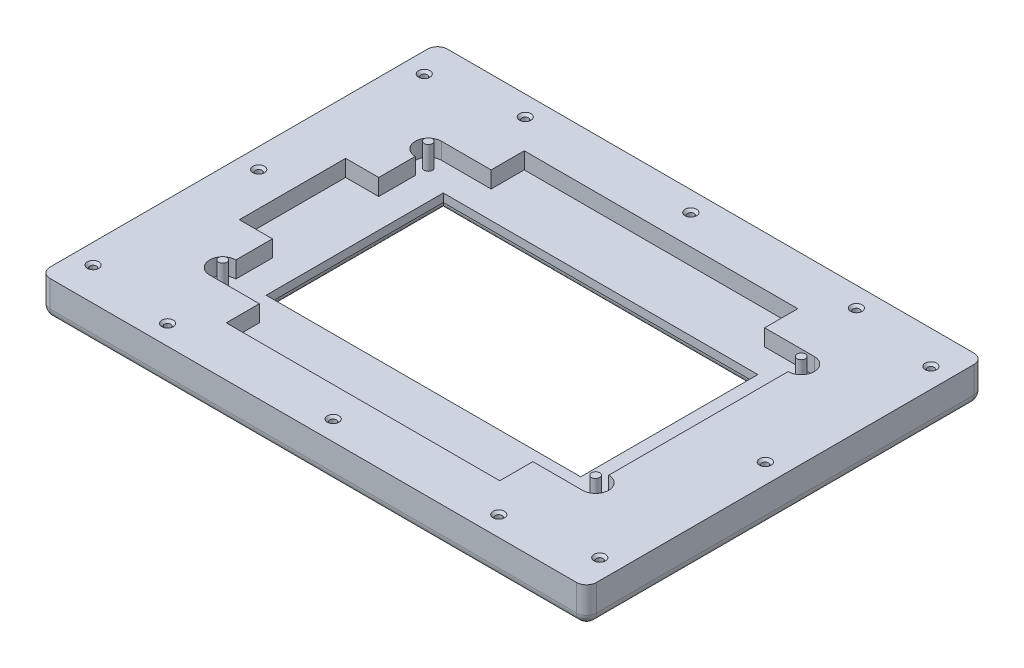
SolidWorks part; units mm, degrees
ref_plane "Front Plane" through (0, 0, 0) normal (0, 0, 1) x (1, 0, 0)
ref_plane "Top Plane" through (0, 0, 0) normal (0, 1, 0) x (1, 0, 0)
ref_plane "Right Plane" through (0, 0, 0) normal (1, 0, 0) x (0, 0, -1)
sketch "Sketch1" plane through (0, 0, 0) normal (0, 1, 0) x (1, 0, 0)
  line L1 (0, 0) -> (165, 0)
  line L2 (0, 0) -> (0, 120)
  line L3 (0, 120) -> (165, 120)
  line L4 (165, 0) -> (165, 120)
  dimension "D1" = 165
  dimension "D2" = 120
extrude "Boss-Extrude1" add sketch "Sketch1" along normal blind 6
sketch "Sketch3" plane through (0, 6, 0) normal (0, 1, 0) x (1, 0, 0)
  line L4 (5, 115) -> (5, 5)
  line L5 (5, 5) -> (160, 5)
  line L6 (160, 5) -> (160, 115)
  line L7 (160, 115) -> (5, 115)
  line L8 (0, 120) -> (0, 0)
  line L9 (0, 0) -> (165, 0)
  line L10 (165, 0) -> (165, 120)
  line L11 (165, 120) -> (0, 120)
  line L12 (0, 120) -> (0, 0)
  line L13 (0, 0) -> (165, 0)
  line L14 (165, 0) -> (165, 120)
  line L15 (165, 120) -> (0, 120)
  dimension "D1" = 0
  dimension "D2" = 5
extrude "Boss-Extrude2" add sketch "Sketch3" along normal blind 5
sketch "Sketch4" plane through (0, 0, 0) normal (0, -1, 0) x (1, 0, 0)
  line L0 (0, 0) -> (82.5, 0)
  line L1 (0, 0) -> (165, 0) construction
  line L2 (82.5, 0) -> (82.5, -120)
  line L3 (165, -120) -> (0, -120) construction
  line L4 (0, -60) -> (165, -60)
  line L5 (0, -120) -> (0, 0) construction
  line L6 (165, 0) -> (165, -120) construction
  line L7 (33, -88.75) -> (33, -31.25)
  line L8 (35, -86.75) -> (130, -86.75)
  line L9 (35, -86.75) -> (35, -33.25)
  line L10 (35, -33.25) -> (130, -33.25)
  line L11 (130, -86.75) -> (130, -33.25)
  line L12 (35, -86.75) -> (130, -33.25) construction
  line L13 (35, -33.25) -> (130, -86.75) construction
  line L14 (33, -31.25) -> (132, -31.25)
  line L15 (132, -88.75) -> (132, -31.25)
  line L16 (33, -88.75) -> (132, -88.75)
  point P14 (82.5, -60)
  dimension "D1" = 95
  dimension "D2" = 53.5
  dimension "D3" = 2
extrude "Acrylic Cutout_3mm" cut sketch "Sketch4" against normal through all contours L10 L9 L4 L2 | L9 L8 L2 L4 | L8 L11 L4 L2 | L4 L11 L10 L2 region at (106.25, 0, -46.625) region at (58.75, 0, -46.625) region at (106.25, 0, -73.375) region at (58.75, 0, -73.375)
extrude "Acrylic Lip" cut sketch "Sketch4<4>" against normal blind 3.5 contours L14 L7 L4 L9 L10 L2 | L7 L16 L2 L8 L9 L4 | L2 L16 L15 L4 L11 L8 | L4 L15 L14 L2 L10 L11 region at (107.25, 0, -31.8224) region at (81.9276, 0, -32.25) region at (34, 0, -60.5724) region at (131.4276, 0, -74.375)
sketch "Sketch4<4>" plane through (0, 0, 0) normal (0, -1, 0) x (1, 0, 0) same geometry as "Sketch4"
sketch "Sketch5" plane through (0, 6, 0) normal (0, 1, 0) x (1, 0, 0)
  line L0 (82.5, 120) -> (82.5, 0)
  line L1 (165, 120) -> (0, 120) construction
  line L2 (0, 0) -> (165, 0) construction
  line L3 (0, 60) -> (165, 60)
  line L4 (0, 120) -> (0, 0) construction
  line L5 (165, 0) -> (165, 120) construction
  line L6 (26.2, 25) -> (138.8, 25)
  line L7 (26.2, 28.95) -> (138.8, 28.95)
  line L8 (26.2, 28.95) -> (26.2, 91.05)
  line L9 (26.2, 91.05) -> (138.8, 91.05)
  line L10 (138.8, 28.95) -> (138.8, 91.05)
  line L11 (26.2, 28.95) -> (138.8, 91.05) construction
  line L12 (26.2, 91.05) -> (138.8, 28.95) construction
  line L13 (26.2, 95) -> (138.8, 95)
  line L14 (138.8, 95) -> (138.8, 25) construction
  line L15 (5, 115) -> (160, 115)
  line L16 (5, 115) -> (5, 5)
  line L17 (5, 5) -> (160, 5)
  line L18 (160, 115) -> (160, 5)
  line L19 (26.2, 95) -> (41.2, 95) construction
  line L20 (41.2, 25) -> (123.8, 25)
  line L21 (41.2, 25) -> (41.2, 15)
  line L22 (41.2, 15) -> (123.8, 15)
  line L23 (123.8, 25) -> (123.8, 15)
  line L24 (26.2, 43.95) -> (16.2, 43.95)
  line L25 (26.2, 43.95) -> (26.2, 76.05)
  line L26 (26.2, 76.05) -> (16.2, 76.05)
  line L27 (16.2, 43.95) -> (16.2, 76.05)
  line L28 (41.2, 95) -> (123.8, 95)
  line L29 (41.2, 95) -> (41.2, 105)
  line L30 (41.2, 105) -> (123.8, 105)
  line L31 (123.8, 95) -> (123.8, 105)
  line L32 (123.8, 95) -> (138.8, 95) construction
  line L33 (138.8, 25) -> (123.8, 25) construction
  line L34 (41.2, 25) -> (26.2, 25) construction
  line L35 (26.2, 32.9) -> (26.2, 43.95) construction
  line L36 (26.2, 76.05) -> (26.2, 91.05) construction
  circle A0 centre (26.2, 91.05) radius 1.25
  circle A1 centre (138.8, 91.05) radius 1.25
  circle A2 centre (138.8, 28.95) radius 1.25
  circle A3 centre (26.2, 28.95) radius 1.25
  circle A4 centre (26.2, 28.95) radius 3.95
  circle A5 centre (26.2, 91.05) radius 3.95
  circle A6 centre (138.8, 28.95) radius 3.95
  circle A7 centre (138.8, 91.05) radius 3.95
  point P12 (82.5, 60)
  line M10 (160, 5) -> (160, 115)
  line M11 (160, 115) -> (5, 115)
  line M12 (5, 115) -> (5, 5)
  line M13 (5, 5) -> (160, 5)
  dimension "D3" = 2.5
  dimension "D4" = 2.5
  dimension "D5" = 2.5
  dimension "D6" = 2.5
  dimension "D7" = 7.9
  dimension "D8" = 7.9
  dimension "D9" = 7.9
  dimension "D10" = 7.9
  dimension "D1" = 112.6
  dimension "D2" = 62.1
  dimension "D11" = 15
  dimension "D12" = 15
  dimension "D13" = 15
  dimension "D14" = 15
  dimension "D15" = 15
  dimension "D16" = 15
  dimension "D17" = 10
  dimension "D18" = 10
  dimension "D19" = 10
extrude "Pegs" add sketch "Sketch5" along normal blind 7 contours L9 A0 L8 | L8 A0 L9 | L8 A3 L7 | L7 A3 L8 | L7 A2 L10 | L10 A2 L7 | L10 A1 L9 | L9 A1 L10 region at (26.7305, 6, -90.5195) region at (26.0232, 6, -91.2268) region at (138.9768, 6, -91.2268) region at (138.2695, 6, -90.5195) region at (138.9768, 6, -28.7732) region at (138.2695, 6, -29.4805) region at (26.0232, 6, -28.7732) region at (26.7305, 6, -29.4805)
extrude "Boss-Extrude4" add sketch "Sketch5<4>" along normal blind 5 contours A5 L13 L0 L3 L8 M11 M12 | A4 L8 L3 L0 L6 M12 M13 | A6 L6 L0 L3 L10 M13 M10 | A7 L10 L3 L0 L13 M10 M11 region at (136.2899, 6, -95.2949) region at (29.4216, 6, -97.8786) region at (29.4216, 6, -22.1214) region at (136.2899, 6, -24.7051)
sketch "Sketch5<4>" plane through (0, 6, 0) normal (0, 1, 0) x (1, 0, 0) same geometry as "Sketch5"
fillet "Fillet1" radius 3 4 edges at (165, 0, -60) (82.5, 0, -120) (82.5, 0, 0) (0, 0, -60)
fillet "Fillet2" radius 1 4 edges at (82.5, 0, -88.75) (33, 0, -60) (82.5, 0, -31.25) (132, 0, -60)
fillet "Fillet3" radius 3 1 edges at (0, 7, -120) type face fillet first side face at (82.5, 7, -120) second side face at (0, 7, -60)
fillet "Fillet4" radius 3 1 edges at (165, 7, -120) type face fillet first side face at (165, 7, -60) second side face at (84, 7, -120)
fillet "Fillet5" radius 3 1 edges at (165, 7, 0) type face fillet first side face at (82.5, 7, 0) second side face at (165, 7, -58.5)
fillet "Fillet6" radius 3 1 edges at (0, 7, 0) type face fillet first side face at (81, 7, 0) second side face at (0, 7, -58.5)
sketch "Sketch6" plane through (0, 11, 0) normal (0, 1, 0) x (1, 0, 0)
  line L0 (0, 60) -> (6, 60) construction
  line L1 (0, 117) -> (0, 3) construction
  line L2 (6, 60) -> (6, 110) construction
  line L4 (82.5, 120) -> (82.5, 114) construction
  line L5 (162, 120) -> (3, 120) construction
  line L6 (82.5, 114) -> (32.5, 114) construction
  circle A0 centre (6, 110) radius 1.375
  circle A1 centre (6, 60) radius 1.375
  circle A2 centre (32.5, 114) radius 1.375
  circle A3 centre (82.5, 114) radius 1.375
  dimension "D5" = 2.75
  dimension "D6" = 2.75
  dimension "D7" = 2.75
  dimension "D8" = 2.75
  dimension "D1" = 6
  dimension "D2" = 6
  dimension "D3" = 50
  dimension "D4" = 50
sketch "Sketch7" plane through (0, 11, 0) normal (0, 1, 0) x (1, 0, 0)
  point P0 (6, 60)
  point P3 (6, 110)
  point P6 (32.5, 114)
  point P9 (82.5, 114)
hole_wizard "#2-64 Tapped Hole1" positions "Sketch7" profile "Sketch8" tap size "#2-64" standard "ANSI Inch"
sketch "Sketch8" plane through (6, 11, -60) normal (1, 0, 0) x (0, 0, 1)
  line L0 (0, 0) -> (0, 5.6009)
  line L1 (0, 5.6009) -> (1, 5)
  line L2 (1, 5) -> (1, 0.7272)
  line L3 (1, 0.7272) -> (1.7272, 0)
  line L5 (1.7272, 0) -> (0, 0)
  line L6 (-1, 0.7272) -> (-1.7272, 0) construction
  line L10 (0, 5.6009) -> (-1, 5) construction
  line L11 (0, -6.35) -> (0, 107.95) construction
  dimension "Tap Drill Dia." = 2
  dimension "Tap Drill Depth" = 5
  dimension "Near C'Sink Dia." = 3.4544
  dimension "Near C'Sink Angle" = 90
  dimension "Drill Angle" = 118
cosmetic thread "Hole Thread1" parameters "D1"=3, "D2"=2.1844
cosmetic thread "Hole Thread2" parameters "D1"=3, "D2"=2.1844
cosmetic thread "Hole Thread3" parameters "D1"=3, "D2"=2.1844
cosmetic thread "Hole Thread4" parameters "D1"=3, "D2"=2.1844
ref_plane "Plane1" through (0, 0, -60) normal (0, 0, 1) x (1, 0, 0)
ref_plane "Plane2" through (82.5, 0, 0) normal (1, 0, 0) x (0, 0, -1)
mirror "Mirror1" about plane through (82.5, 0, 0) normal (1, 0, 0) of "#2-64 Tapped Hole1" second plane through (0, 0, -60) second plane normal (0, 0, 1)
cosmetic thread "Hole Thread5" parameters "D1"=3, "D2"=2.1844
cosmetic thread "Hole Thread6" parameters "D1"=3, "D2"=2.1844
cosmetic thread "Hole Thread7" parameters "D1"=3, "D2"=2.1844
cosmetic thread "Hole Thread8" parameters "D1"=3, "D2"=2.1844
cosmetic thread "Hole Thread9" parameters "D1"=3, "D2"=2.1844
cosmetic thread "Hole Thread10" parameters "D1"=3, "D2"=2.1844
cosmetic thread "Hole Thread11" parameters "D1"=3, "D2"=2.1844
cosmetic thread "Hole Thread12" parameters "D1"=3, "D2"=2.1844
